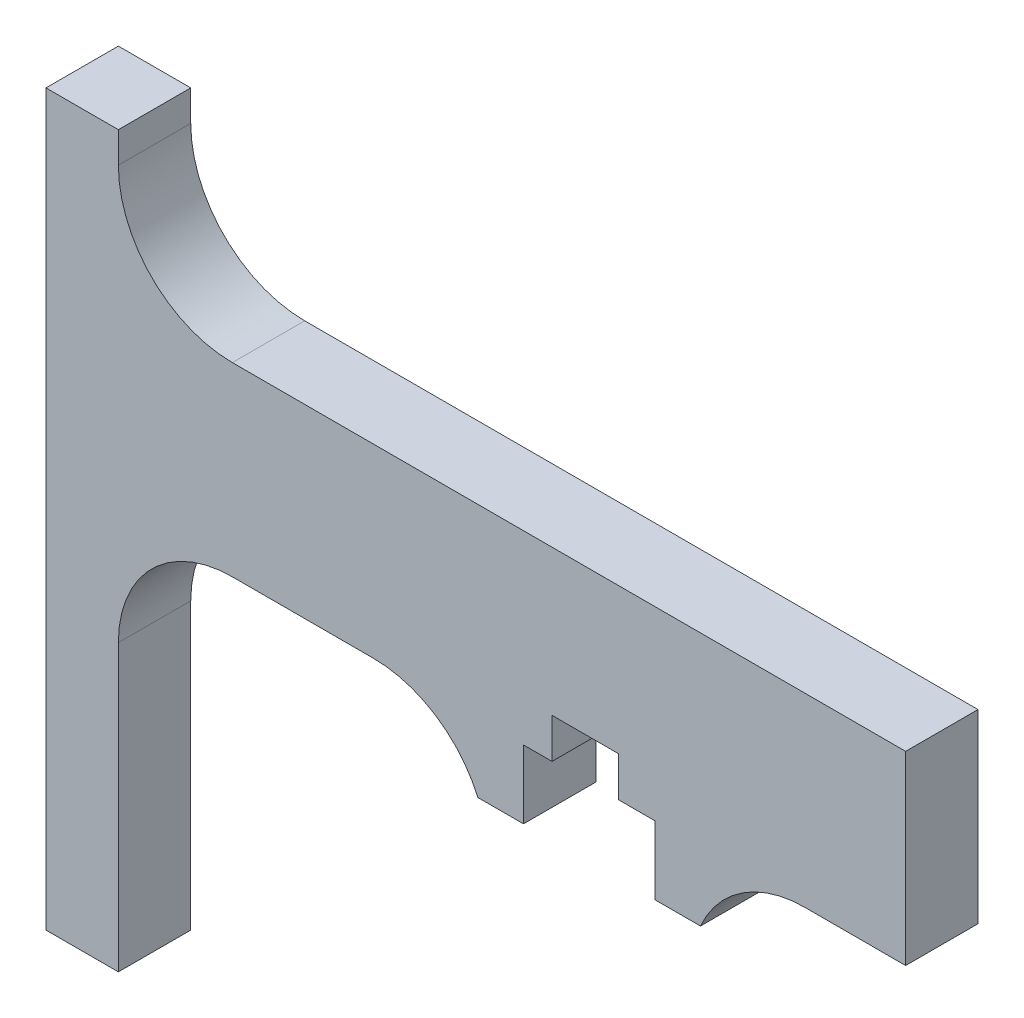
SolidWorks part; units mm, degrees
ref_plane "Front Plane" through (0, 0, 0) normal (0, 0, 1) x (1, 0, 0)
ref_plane "Top Plane" through (0, 0, 0) normal (0, 1, 0) x (1, 0, 0)
ref_plane "Right Plane" through (0, 0, 0) normal (1, 0, 0) x (0, 0, -1)
sketch "Sketch2" plane through (0, 0, 0) normal (0, 0, 1) x (1, 0, 0)
  line L0 (0, -45.0015) -> (0, 0)
  line L1 (0, 0) -> (6.35, 0)
  line L2 (6.35, 0) -> (6.35, -12.7)
  line L3 (6.35, -12.7) -> (75.4271, -12.7)
  line L4 (75.4271, -12.7) -> (75.4271, -28.978)
  line L5 (75.4271, -28.978) -> (6.35, -28.978)
  line L6 (6.35, -28.978) -> (6.35, -63.9998)
  line L7 (6.35, -63.9998) -> (0, -63.9998)
  line L8 (0, -63.9998) -> (0, -45.0015)
  dimension "D1" = 12.7
  dimension "D2" = 35.0218
  dimension "D3" = 16.278
  dimension "D4" = 6.35
  dimension "D5" = 69.0771
  dimension "D6" = 63.9998
extrude "Boss-Extrude1" add sketch "Sketch2" along normal blind 6.35
fillet "Fillet1" radius 10 2 edges at (6.35, -28.978, 3.175) (6.35, -12.7, 3.175)
sketch "Sketch3" plane through (0, 0, 0) normal (0, 0, -1) x (-1, 0, 0)
  line L0 (-16.35, -28.978) -> (-75.4271, -28.978) construction
  line L1 (-37.8971, -28.978) -> (-41.8971, -28.978)
  line L2 (-37.8971, -28.978) -> (-37.8971, -34.978)
  line L3 (-37.8971, -34.978) -> (-41.8971, -34.978)
  line L4 (-41.8971, -28.978) -> (-41.8971, -34.978)
  line L6 (-53.4271, -28.978) -> (-57.4271, -28.978)
  line L7 (-53.4271, -28.978) -> (-53.4271, -34.978)
  line L8 (-53.4271, -34.978) -> (-57.4271, -34.978)
  line L9 (-57.4271, -28.978) -> (-57.4271, -34.978)
  dimension "D1" = 4
  dimension "D2" = 4
  dimension "D3" = 11.53
  dimension "D4" = 18
  dimension "D5" = 6
  dimension "D6" = 6
extrude "Boss-Extrude2" add sketch "Sketch3" against normal blind 6.35
fillet "Fillet2" radius 10 2 edges at (57.4271, -28.978, 3.175) (37.8971, -28.978, 3.175)
sketch "Sketch4" plane through (0, 0, 0) normal (0, 0, -1) x (-1, 0, 0)
  line L0 (-41.8971, -28.978) -> (-53.4271, -28.978) construction
  line L1 (-50.2506, -28.978) -> (-44.4006, -28.978)
  line L2 (-50.2506, -28.978) -> (-50.2506, -25.478)
  line L3 (-50.2506, -25.478) -> (-44.4006, -25.478)
  line L4 (-44.4006, -28.978) -> (-44.4006, -25.478)
  dimension "D1" = 5.85
  dimension "D2" = 3.1765
  dimension "D3" = 2.5035
  dimension "D4" = 3.5
extrude "Cut-Extrude1" cut sketch "Sketch4" against normal blind 10
equation "\"D1@Sketch4\" = \"Material@RudderBox.SLDASM\""
